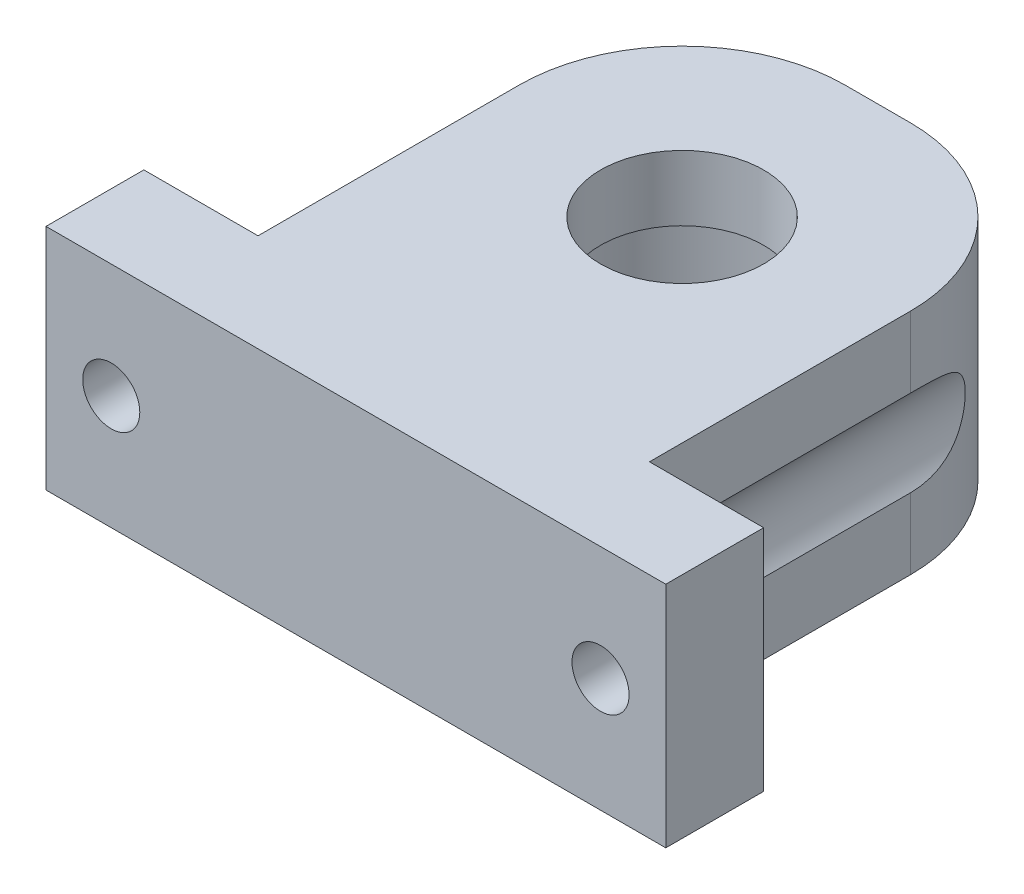
SolidWorks part; units mm, degrees
ref_plane "Front Plane" through (0, 0, 0) normal (0, 0, 1) x (1, 0, 0)
ref_plane "Top Plane" through (0, 0, 0) normal (0, 1, 0) x (1, 0, 0)
ref_plane "Right Plane" through (0, 0, 0) normal (1, 0, 0) x (0, 0, -1)
sketch "Sketch1" plane through (0, 0, 0) normal (0, 1, 0) x (1, 0, 0)
  line L1 (-19, 0) -> (19, 0)
  line L2 (19, 0) -> (19, 6)
  line L3 (-12, 32) -> (12, 32)
  line L4 (0, 32) -> (0, 0)
  line L5 (12, 32) -> (12, 6)
  line L6 (12, 6) -> (19, 6)
  line L7 (-12, 32) -> (-12, 6)
  line L8 (-19, 0) -> (-19, 6)
  line L9 (-12, 6) -> (-19, 6)
  circle A0 centre (0, 20) radius 8.15
  dimension "D2" = 16.3
  dimension "D6" = 20
  dimension "D1" = 19
  dimension "D3" = 6
  dimension "D4" = 32
  dimension "D5" = 12
extrude "Boss-Extrude1" add sketch "Sketch1" along normal blind 7 and the other way blind 7 contours A0 L3 L7 L9 L8 L1 L4 | A0 L4 L1 L2 L6 L5 L3 region at (-8.0646, 0, -13.0051) region at (8.0646, 0, -13.0051)
sketch "Sketch2" plane through (0, 0, 0) normal (0, 0, 1) x (1, 0, 0)
  line L0 (0, 7) -> (0, -7) construction
  line L1 (-19, 7) -> (19, 7) construction
  line L2 (-19, -7) -> (19, -7) construction
  line L3 (-19, 0) -> (19, 0) construction
  line L4 (-19, -7) -> (-19, 7) construction
  line L5 (19, -7) -> (19, 7) construction
  circle A0 centre (-15, 0) radius 1.75
  circle A1 centre (15, 0) radius 1.75
  dimension "D1" = 3.5
  dimension "D2" = 15
extrude "Cut-Extrude1" cut sketch "Sketch2" against normal up to next
fillet "Fillet1" radius 10 2 edges at (-12, 0, -32) (12, 0, -32)
sketch "Sketch3" plane through (0, 7, 0) normal (0, 1, 0) x (1, 0, 0)
  circle A0 centre (0, 20) radius 8.9988
  circle A1 centre (0, 20) radius 5
  dimension "D1" = 17.9976
  dimension "D2" = 10
extrude "Boss-Extrude2" add sketch "Sketch3" against normal blind 4
sketch "Sketch4" plane through (0, 0, -6) normal (0, 0, -1) x (-1, 0, 0)
  line L0 (0, -7) -> (0, 7) construction
  line L1 (2, -7) -> (-2, -7) construction
  line L2 (2, 7) -> (-2, 7) construction
  circle A0 centre (15, 0) radius 4
  circle A1 centre (-15, 0) radius 4
  dimension "D1" = 8
extrude "Cut-Extrude2" cut sketch "Sketch4" along normal up to next
